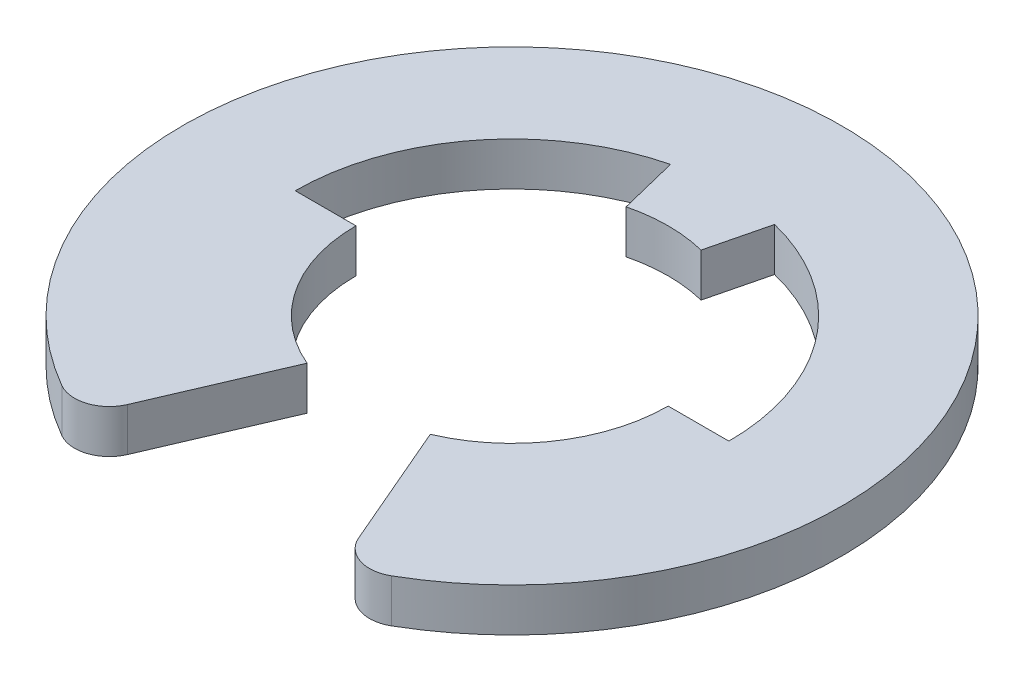
SolidWorks part; units mm, degrees
ref_plane "Front Plane" through (0, 0, 0) normal (0, 0, 1) x (1, 0, 0)
ref_plane "Top Plane" through (0, 0, 0) normal (0, 1, 0) x (1, 0, 0)
ref_plane "Right Plane" through (0, 0, 0) normal (1, 0, 0) x (0, 0, -1)
sketch "Sketch2" plane through (0, 0, 0) normal (0, 1, 0) x (1, 0, 0)
  line L1 (-3.175, 0) -> (-2.286, 0)
  line L2 (0, 0) -> (0, 3.175) construction
  line L3 (0, 0) -> (0.762, 3.0822) construction
  line L9 (0, 0) -> (-0.762, 3.0822) construction
  line L10 (-0.762, 3.0822) -> (-0.5486, 2.2192)
  line L11 (0.762, 3.0822) -> (0.5486, 2.2192)
  line L12 (-0.9024, -2.1004) -> (-1.905, -4.4341)
  line L13 (0.9024, -2.1004) -> (1.905, -4.4341)
  line L14 (2.286, 0) -> (3.175, 0)
  arc A6 (1.905, -4.4341) -> (-1.905, -4.4341) centre (0, 0) ccw
  arc A7 (3.175, 0) -> (0.762, 3.0822) centre (0, 0) ccw
  arc A8 (0.9024, -2.1004) -> (2.286, 0) centre (0, 0) ccw
  arc A9 (-0.762, 3.0822) -> (-3.175, 0) centre (0, 0) ccw
  arc A10 (-2.286, 0) -> (-0.9024, -2.1004) centre (0, 0) ccw
  arc A11 (0.5486, 2.2192) -> (-0.5486, 2.2192) centre (0, 0) ccw
  point P16 (0, 0)
  point P17 (0, 0)
  dimension "D1" = 9.652
  dimension "D2" = 6.35
  dimension "D3" = 4.572
  dimension "D4" = 3.81
  dimension "D5" = 1.524
extrude "Boss-Extrude1" add sketch "Sketch2" along normal mid plane 0.635
fillet "Fillet1" radius 0.508 2 edges at (1.905, 0, 4.4341) (-1.905, 0, 4.4341)
